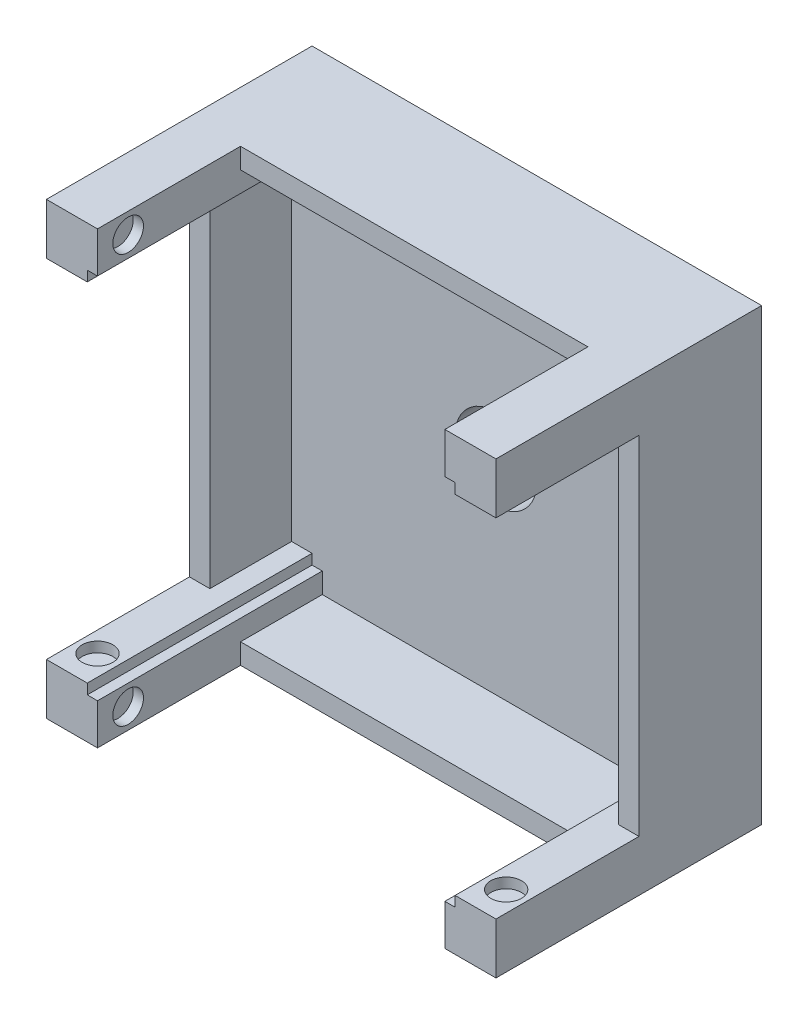
SolidWorks part; units mm, degrees
ref_plane "前视基准面" through (0, 0, 0) normal (0, 0, 1) x (1, 0, 0)
ref_plane "上视基准面" through (0, 0, 0) normal (0, 1, 0) x (1, 0, 0)
ref_plane "右视基准面" through (0, 0, 0) normal (1, 0, 0) x (0, 0, -1)
sketch "草图1" plane through (0, 0, 0) normal (0, 0, 1) x (1, 0, 0)
  line L1 (-110, -110) -> (110, -110)
  line L2 (-110, -110) -> (-110, 110)
  line L3 (-110, 110) -> (110, 110)
  line L4 (110, -110) -> (110, 110)
  line L5 (-110, -110) -> (110, 110) construction
  line L6 (-110, 110) -> (110, -110) construction
  point P0 (0, 0)
  dimension "D1" = 220
extrude "凸台-拉伸1" add sketch "草图1" along normal blind 20
sketch "草图2" plane through (0, 0, 20) normal (0, 0, 1) x (1, 0, 0)
  line L0 (85, 110) -> (110, 110)
  line L1 (110, 110) -> (-110, 110) construction
  line L2 (110, 110) -> (110, 85)
  line L3 (110, -110) -> (110, 110) construction
  line L4 (110, 85) -> (90, 85)
  line L5 (85, 110) -> (85, 90)
  line L6 (90, 85) -> (90, 90)
  line L7 (90, 90) -> (85, 90)
  line L8 (0, -110) -> (0, 110) construction
  line L10 (-110, -110) -> (110, -110) construction
  line L11 (-110, 0) -> (110, 0) construction
  line L12 (-110, 110) -> (-110, -110) construction
  dimension "D1" = 25
  dimension "D2" = 20
extrude "凸台-拉伸3" add sketch "草图2" along normal blind 110
sketch "草图4" plane through (0, 85, 0) normal (0, -1, 0) x (-1, 0, 0)
  line L0 (-90, -130) -> (-110, -130) construction
  line L1 (-90, -130) -> (-90, -20) construction
  circle A0 centre (-100, -115) radius 7.5
  dimension "D1" = 15
  dimension "D2" = 15
  dimension "D3" = 10
extrude "切除-拉伸2" cut sketch "草图4" against normal blind 5
sketch "草图7" plane through (85, 0, 0) normal (-1, 0, 0) x (0, 0, 1)
  line L0 (130, 110) -> (130, 90) construction
  line L1 (130, 110) -> (20, 110) construction
  circle A0 centre (115, 100) radius 7.5
  dimension "D1" = 15
  dimension "D2" = 15
  dimension "D3" = 10
extrude "切除-拉伸3" cut sketch "草图7" against normal blind 5
mirror "镜向2" about plane through (0, 0, 0) normal (1, 0, 0) of "凸台-拉伸1", "切除-拉伸3", "切除-拉伸2", "凸台-拉伸3"
mirror "镜向5" about plane through (0, 0, 0) normal (0, 1, 0) of "镜向2"
sketch "草图10" plane through (110, 0, 0) normal (1, 0, 0) x (0, 0, -1)
  line L0 (-60, 85) -> (-60, -85)
  line L1 (-130, 85) -> (-20, 85) construction
  line L2 (-130, -85) -> (-20, -85) construction
  line L3 (-20, -85) -> (-20, 85) construction
  line L4 (-60, -85) -> (-20, -85)
  line L5 (-20, -85) -> (-20, 85)
  line L6 (-20, 85) -> (-60, 85)
  dimension "D1" = 40
extrude "凸台-拉伸5" add sketch "草图10" against normal blind 10
sketch "草图11" plane through (0, -110, 0) normal (0, -1, 0) x (1, 0, 0)
  line L0 (-85, 60) -> (85, 60)
  line L1 (-85, 130) -> (-85, 20) construction
  line L2 (85, 130) -> (85, 20) construction
  line L3 (-85, 20) -> (85, 20) construction
  line L4 (-85, 60) -> (-85, 20)
  line L5 (-85, 20) -> (85, 20)
  line L6 (85, 20) -> (85, 60)
  dimension "D1" = 40
extrude "凸台-拉伸6" add sketch "草图11" against normal blind 10
sketch "草图12" plane through (-110, 0, 0) normal (-1, 0, 0) x (0, 0, 1)
  line L0 (60, 85) -> (60, -85)
  line L1 (60, -85) -> (20, -85)
  line L2 (20, -85) -> (20, 85)
  line L3 (20, 85) -> (60, 85)
extrude "凸台-拉伸7" add sketch "草图12" against normal blind 10
sketch "草图13" plane through (0, 110, 0) normal (0, 1, 0) x (1, 0, 0)
  line L0 (-85, -60) -> (85, -60)
  line L1 (85, -60) -> (85, -20)
  line L2 (85, -130) -> (85, -20) construction
  line L3 (85, -20) -> (85, -60) construction
  line L4 (85, -20) -> (-85, -20)
  line L5 (-85, -20) -> (-85, -60)
extrude "凸台-拉伸8" add sketch "草图13" against normal blind 10
sketch "草图16" plane through (0, 0, 20) normal (0, 0, 1) x (1, 0, 0)
  circle A0 centre (0, 0) radius 20
  dimension "D1" = 40
extrude "切除-拉伸6" cut sketch "草图16" against normal up to surface (20 mm away) contours A0 up to face at (0, 0, 0)
